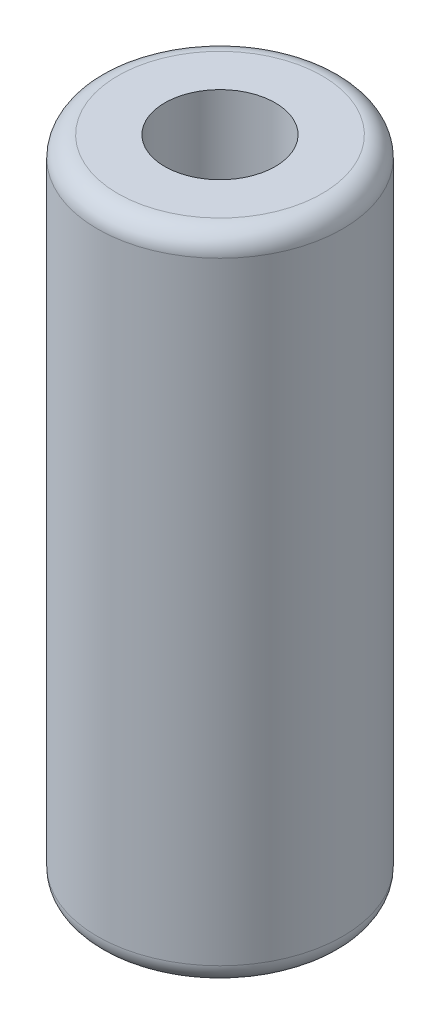
SolidWorks part; units mm, degrees
material "1060 Alloy"
ref_plane "Front Plane" through (0, 0, 0) normal (0, 0, 1) x (1, 0, 0)
ref_plane "Top Plane" through (0, 0, 0) normal (0, 1, 0) x (1, 0, 0)
ref_plane "Right Plane" through (0, 0, 0) normal (1, 0, 0) x (0, 0, -1)
sketch "Sketch1" plane through (0, 0, 0) normal (0, 1, 0) x (1, 0, 0)
  circle A0 centre (0, 0) radius 3
  dimension "D1" = 6
extrude "Boss-Extrude1" add sketch "Sketch1" along normal blind 8 and the other way blind 8
hole_wizard "#6-32 Tapped Hole1" positions "Sketch3" profile "Sketch2" tap size "#6-32" standard "ANSI Inch"
sketch "Sketch3" plane through (0, 8, 0) normal (0, 1, 0) x (1, 0, 0)
  point P5 (0, 0)
sketch "Sketch2" plane through (0, 8, 0) normal (1, 0, 0) x (0, 0, 1)
  line L0 (0, 0) -> (0, 7.8127)
  line L1 (0, 7.8127) -> (1.3525, 7)
  line L2 (1.3525, 7) -> (1.3525, 0)
  line L5 (1.3525, 0) -> (0, 0)
  line L10 (0, 7.8127) -> (-1.3526, 7) construction
  line L11 (0, -6.35) -> (0, 107.95) construction
  dimension "Tap Drill Dia." = 2.7051
  dimension "Tap Drill Depth" = 7
  dimension "Drill Angle" = 118
cosmetic thread "Hole Thread1"
hole_wizard "#6-32 Tapped Hole2" positions "Sketch6" profile "Sketch5" tap size "#6-32" standard "ANSI Inch"
sketch "Sketch6" plane through (0, -8, 0) normal (0, -1, 0) x (-1, 0, 0)
  point P0 (0, 0)
sketch "Sketch5" plane through (0, -8, 0) normal (1, 0, 0) x (0, 0, -1)
  line L0 (0, 0) -> (0, 7.8127)
  line L1 (0, 7.8127) -> (1.3525, 7)
  line L2 (1.3525, 7) -> (1.3525, 0)
  line L5 (1.3525, 0) -> (0, 0)
  line L10 (0, 7.8127) -> (-1.3526, 7) construction
  line L11 (0, -6.35) -> (0, 107.95) construction
  dimension "Tap Drill Dia." = 2.7051
  dimension "Tap Drill Depth" = 7
  dimension "Drill Angle" = 118
cosmetic thread "Hole Thread2"
fillet "Fillet1" radius 0.5 2 edges at (0, -8, 3) (0, 8, 3)
